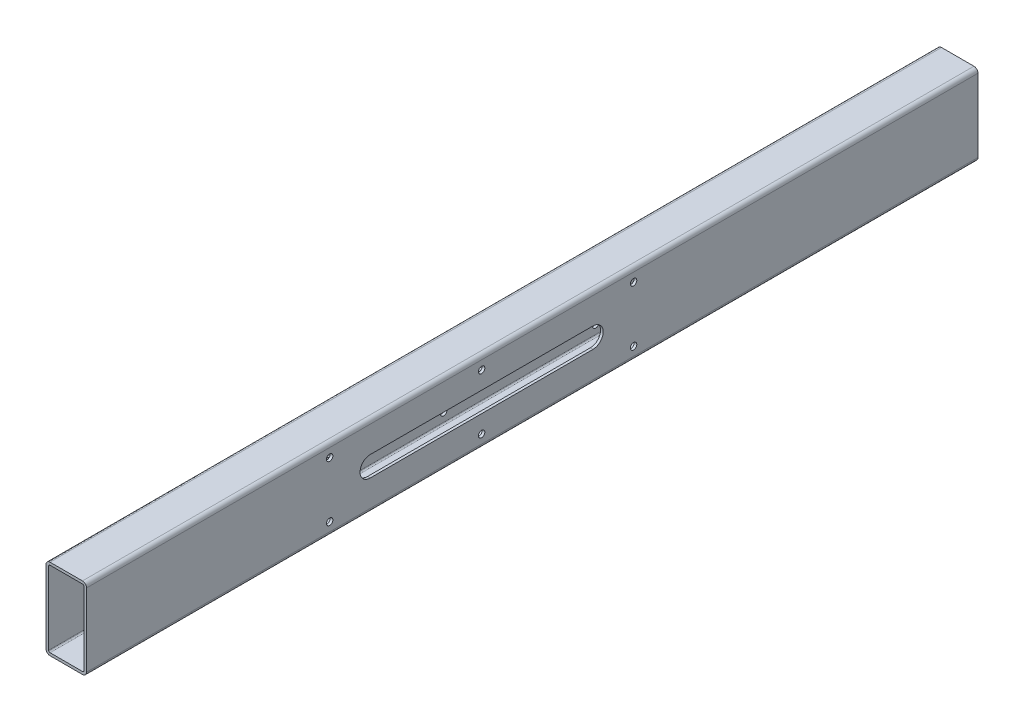
SolidWorks part; units mm, degrees
material "6061-T6 (SS)"
ref_plane "Front Plane" through (0, 0, 0) normal (0, 0, 1) x (1, 0, 0)
ref_plane "Top Plane" through (0, 0, 0) normal (0, 1, 0) x (1, 0, 0)
ref_plane "Right Plane" through (0, 0, 0) normal (1, 0, 0) x (0, 0, -1)
sketch "Sketch1" plane through (0, 0, 0) normal (0, 0, 1) x (1, 0, 0)
  line L1 (10.16, -25.4) -> (-10.16, -25.4)
  line L2 (12.7, -22.86) -> (12.7, 22.86)
  line L3 (10.16, 25.4) -> (-10.16, 25.4)
  line L4 (-12.7, -22.86) -> (-12.7, 22.86)
  line L5 (12.7, -25.4) -> (-12.7, 25.4) construction
  line L6 (12.7, 25.4) -> (-12.7, -25.4) construction
  arc A0 (-10.16, -25.4) -> (-12.7, -22.86) centre (-10.16, -22.86) cw
  arc A1 (10.16, -25.4) -> (12.7, -22.86) centre (10.16, -22.86) ccw
  arc A2 (12.7, 22.86) -> (10.16, 25.4) centre (10.16, 22.86) ccw
  arc A3 (-10.16, 25.4) -> (-12.7, 22.86) centre (-10.16, 22.86) ccw
  point P0 (0, 0)
  dimension "D3" = 2.54
  dimension "D1" = 25.4
  dimension "D2" = 50.8
extrude "Extrude-Thin1" add sketch "Sketch1" along normal mid plane 558.8 thin thin type one direction reverse wall 1.651
sketch "Sketch2" [suppressed] plane through (-12.7, 0, 0) normal (-1, 0, 0) x (0, 0, 1)
  line L0 (25.4, 0) -> (152.4, 0) construction
  line L1 (25.4, 6.35) -> (152.4, 6.35)
  line L2 (25.4, -6.35) -> (152.4, -6.35)
  line L3 (0, 22.86) -> (0, -22.86) construction
  arc A0 (25.4, 6.35) -> (25.4, -6.35) centre (25.4, 0) ccw
  arc A1 (152.4, -6.35) -> (152.4, 6.35) centre (152.4, 0) ccw
  point P3 (88.9, 0)
  dimension "D1" = 12.7
  dimension "D2" = 127
  dimension "D3" = 25.4
extrude "Cut-Extrude1" [suppressed] cut sketch "Sketch2" against normal through all
sketch "Sketch3" plane through (-12.7, 0, 0) normal (-1, 0, 0) x (0, 0, 1)
  line L0 (101.6, 0) -> (-38.1, 0) construction
  line L1 (101.6, -6.35) -> (-38.1, -6.35)
  line L2 (101.6, 6.35) -> (-38.1, 6.35)
  line L3 (279.4, 22.86) -> (279.4, -22.86) construction
  arc A0 (101.6, -6.35) -> (101.6, 6.35) centre (101.6, 0) ccw
  arc A1 (-38.1, 6.35) -> (-38.1, -6.35) centre (-38.1, 0) ccw
  point P3 (31.75, 0)
  dimension "D1" = 12.7
  dimension "D2" = 177.8
  dimension "D3" = 139.7
extrude "Cut-Extrude2" cut sketch "Sketch3" against normal through all
sketch "Sketch5" plane through (12.7, 0, 0) normal (1, 0, 0) x (0, 0, -1)
  circle A0 centre (63.5, 17.399) radius 2.0193 construction
  circle A1 centre (63.5, -17.399) radius 2.0193 construction
  circle A2 centre (-31.75, 17.399) radius 2.0193 construction
  circle A3 centre (-31.75, -17.399) radius 2.0193 construction
  circle A4 centre (-127, -17.399) radius 2.0193 construction
  circle A5 centre (-127, 17.399) radius 2.0193 construction
  circle A6 centre (63.5, 17.399) radius 2.0193
  circle A7 centre (63.5, -17.399) radius 2.0193
  circle A8 centre (-31.75, 17.399) radius 2.0193
  circle A9 centre (-31.75, -17.399) radius 2.0193
  circle A10 centre (-127, -17.399) radius 2.0193
  circle A11 centre (-127, 17.399) radius 2.0193
extrude "Cut-Extrude3" cut sketch "Sketch5" against normal through all
